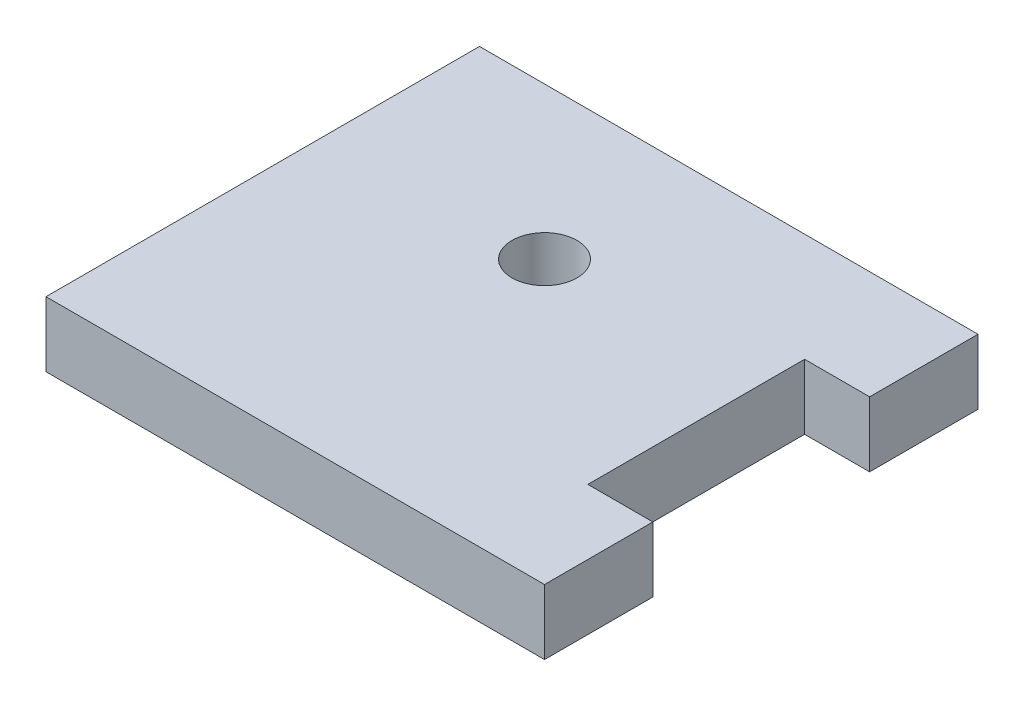
SolidWorks part; units mm, degrees
ref_plane "Front Plane" through (0, 0, 0) normal (0, 0, 1) x (1, 0, 0)
ref_plane "Top Plane" through (0, 0, 0) normal (0, 1, 0) x (1, 0, 0)
ref_plane "Right Plane" through (0, 0, 0) normal (1, 0, 0) x (0, 0, -1)
sketch "Sketch1" plane through (0, 0, 0) normal (0, 1, 0) x (1, 0, 0)
  line L0 (10, 20) -> (10, 0) construction
  line L1 (0, 0) -> (20, 0)
  line L2 (0, 0) -> (0, 20)
  line L3 (0, 20) -> (20, 20)
  line L4 (20, 5) -> (20, 15)
  line L10 (20, 5) -> (23, 5)
  line L11 (20, 20) -> (23, 20)
  line L13 (20, 15) -> (23, 15)
  line L14 (23, 20) -> (23, 15)
  line L15 (23, 0) -> (23, 5)
  line L16 (20, 0) -> (23, 0)
  circle A0 centre (10, 13) radius 1.5
  dimension "D1" = 20
  dimension "D2" = 20
  dimension "D3" = 3
  dimension "D4" = 5
  dimension "D5" = 7
extrude "Boss-Extrude1" add sketch "Sketch1" along normal blind 3
